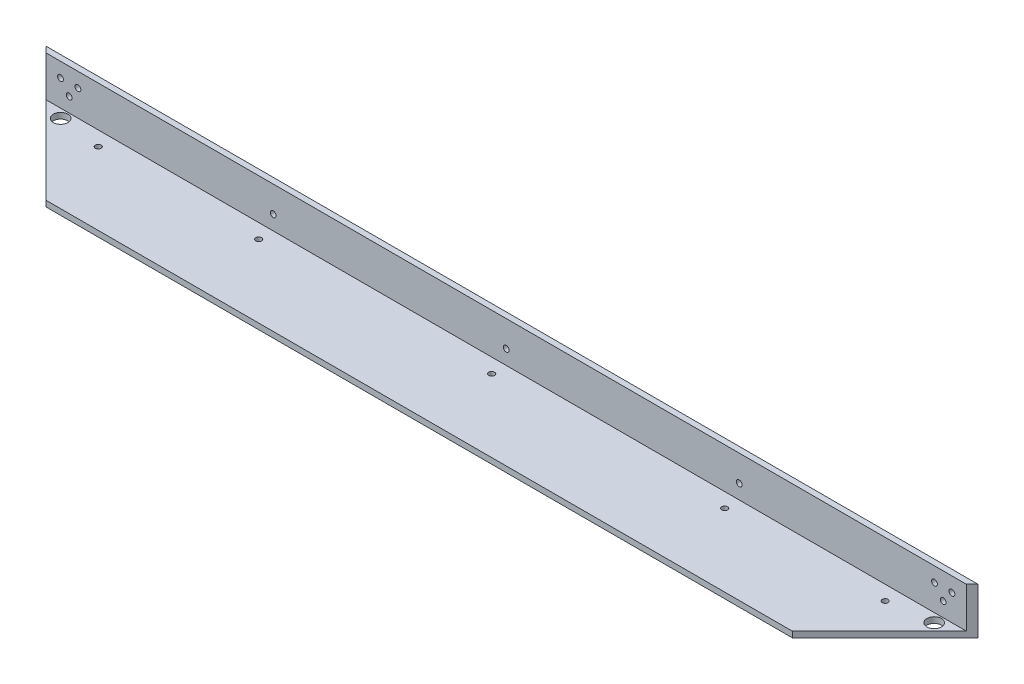
SolidWorks part; units mm, degrees
ref_plane "Front Plane" through (0, 0, 0) normal (0, 0, 1) x (1, 0, 0)
ref_plane "Top Plane" through (0, 0, 0) normal (0, 1, 0) x (1, 0, 0)
ref_plane "Right Plane" through (0, 0, 0) normal (1, 0, 0) x (0, 0, -1)
sketch "Sketch1" plane through (0, 0, 0) normal (1, 0, 0) x (0, 0, -1)
  line L0 (0, 0) -> (-50.8, 0)
  line L1 (-50.8, 0) -> (-50.8, 3.175)
  line L2 (-50.8, 3.175) -> (-3.175, 3.175)
  line L3 (-3.175, 3.175) -> (-3.175, 25.4)
  line L4 (-3.175, 25.4) -> (0, 25.4)
  line L5 (0, 25.4) -> (0, 0)
  dimension "LHeight" = 25.4
  dimension "LWidth" = 50.8
  dimension "LMaterialThickness" = 3.175
  dimension "D1" = 47.625
  dimension "D2" = 22.225
  dimension "D3" = 3.175
extrude "Boss-Extrude1" add sketch "Sketch1" along normal blind 510
chamfer "Chamfer6" distance 50.8 angle 45 1 edges at (510, 1.5875, 50.8)
chamfer "Chamfer7" distance 50.8 angle 45 1 edges at (0, 1.5875, 50.8)
sketch "BackSideHoles-Sketch2" plane through (0, 0, 0) normal (0, 0, -1) x (-1, 0, 0)
  line L0 (0, 0) -> (0, 25.4) construction
  line L1 (-510, 0) -> (0, 0) construction
  line L2 (-510, 0) -> (-510, 25.4) construction
  line L3 (-510, 25.4) -> (0, 25.4) construction
  circle A0 centre (-498.8875, 17.4625) radius 1.5875
  circle A1 centre (-489.3625, 17.4625) radius 1.5875
  circle A2 centre (-20.6375, 17.4625) radius 1.5875
  circle A4 centre (-11.1125, 17.4625) radius 1.5875
  circle A5 centre (-15.875, 11.1125) radius 1.5875
  circle A6 centre (-494.125, 11.1125) radius 1.5875
  circle A8 centre (-382.5, 11.1125) radius 1.5875
  circle A9 centre (-255, 11.1125) radius 1.5875
  circle A10 centre (-127.5, 11.1125) radius 1.5875
  dimension "D5" = 3.175
  dimension "D2" = 20.6375
  dimension "D4" = 20.6375
  dimension "D8" = 127.5
  dimension "D9" = 127.5
  dimension "D10" = 127.5
  dimension "D11" = 11.1125
  dimension "D6" = 7.9375
  dimension "D7" = 11.1125
  dimension "D3" = 11.1125
  dimension "D12" = 15.875
  dimension "D13" = 15.875
sketch "BottomHoles-Sketch3" plane through (0, 0, 0) normal (0, -1, 0) x (1, 0, 0)
  line L0 (510, 0) -> (0, 0) construction
  circle A7 centre (39.6875, 11.1125) radius 1.5875
  circle A8 centre (470.3125, 11.1125) radius 1.5875
  circle A9 centre (127.5, 11.1125) radius 1.5875
  circle A10 centre (255, 11.1125) radius 1.5875
  circle A11 centre (382.5, 11.1125) radius 1.5875
  circle A12 centre (494, 8) radius 4
  circle A13 centre (16, 8) radius 4
  point P21 (13.8721, 4.5045)
  dimension "D5" = 3.175
  dimension "D11" = 8
  dimension "D2" = 39.6875
  dimension "D3" = 39.6875
  dimension "D4" = 11.1125
  dimension "D1" = 127.5
  dimension "D6" = 127.5
  dimension "D7" = 127.5
  dimension "D8" = 16
  dimension "D9" = 8
  dimension "D10" = 16
extrude "BottomHoles-Cut-Extrude1" cut sketch "BottomHoles-Sketch3" against normal through all
extrude "BackSideHoles-Cut-Extrude2" cut sketch "BackSideHoles-Sketch2" against normal through all
equation "\"LowerRailWidth\"= 2.00in"
equation "\"LowerRailHeight\"= 1.00in"
equation "\"RailThickness\"= .125in'Spec"
equation "\"SideRailHoleX1FromSide\"= \"HoleOffsetFromSide\""
equation "\"SideRailHoleX2FromSide\"= \"VSWidth\" - \"HoleOffsetFromEdge\" - \"RailThickness\"'Equals 20.6375"
equation "\"SideRailHoleY1FromEdge\"= \"HoleOffsetFromEdge\""
equation "\"FrontBackRailLength\"= 510mm"
equation "\"VSWidth\"= 1.25in'Spec"
equation "\"HoleOffsetFromEdge\"= \"RailThickness\" * 2.5"
equation "\"HoleOffsetFromSide\"= \"RailThickness\" * 3.5"
equation "\"SideRailHoleY2FromSide\"= \"HoleOffsetFromSide\""
equation "\"FasteningHoleDiameter\"= .125in"
equation "\"D1@Boss-Extrude1\"=\"FrontBackRailLength\""
equation "\"D1@Chamfer6\"=\"LowerRailWidth\""
equation "\"D1@Chamfer7\"=\"LowerRailWidth\""
equation "\"D2@BackSideHoles-Sketch2\" = \"SideRailHoleX2FromSide\""
equation "\"D4@BackSideHoles-Sketch2\" = \"SideRailHoleX2FromSide\""
equation "\"D5@BackSideHoles-Sketch2\" = \"FasteningHoleDiameter\""
equation "\"LHeight@Sketch1\"=\"LowerRailHeight\""
equation "\"LWidth@Sketch1\"=\"LowerRailWidth\""
equation "\"LowerCornerBlockWidth\"= \"LowerRailWidth\" - \"RailThickness\" * 2'Room for left front stepper"
equation "\"D2@BottomHoles-Sketch3\"=\"CornerEnclosureOffset\""
equation "\"D3@BottomHoles-Sketch3\"=\"CornerEnclosureOffset\""
equation "\"D4@BottomHoles-Sketch3\"=\"LowerCornerBlockY1FromSide\""
equation "\"D5@BottomHoles-Sketch3\"=\"FasteningHoleDiameter\""
equation "\"CornerEnclosureOffset\"= \"LowerCornerBlockWidth\" - \"HoleOffsetFromEdge\" + \"RailThickness\""
equation "\"LowerCornerBlockY1FromSide\"= \"HoleOffsetFromSide\""
equation "\"FrontOrBackEnclosureOffsets\"= \"FrontBackRailLength\" / 4"
equation "\"D1@BottomHoles-Sketch3\"=\"FrontOrBackEnclosureOffsets\""
equation "\"D6@BottomHoles-Sketch3\"=\"FrontOrBackEnclosureOffsets\""
equation "\"D7@BottomHoles-Sketch3\"=\"FrontOrBackEnclosureOffsets\""
equation "\"D8@BackSideHoles-Sketch2\"=\"FrontOrBackEnclosureOffsets\""
equation "\"D9@BackSideHoles-Sketch2\"=\"FrontOrBackEnclosureOffsets\""
equation "\"D10@BackSideHoles-Sketch2\"=\"FrontOrBackEnclosureOffsets\""
equation "\"D11@BackSideHoles-Sketch2\"=\"SideRailHoleX1FromSide\""
equation "\"D6@BackSideHoles-Sketch2\"=\"SideRailHoleY1FromEdge\""
equation "\"D7@BackSideHoles-Sketch2\"=\"SideRailHoleY2FromSide\""
equation "\"D3@BackSideHoles-Sketch2\"=\"SideRailHoleX1FromSide\""
equation "\"VSMidSideRailHoleXFromSideToCenter\"= \"RailThickness\" * 6"
equation "\"D12@BackSideHoles-Sketch2\"=\"VSMidSideRailHoleXFromSideToCenter\" - \"RailThickness\""
equation "\"D13@BackSideHoles-Sketch2\"=\"VSMidSideRailHoleXFromSideToCenter\" - \"RailThickness\""
equation "\"LowerRailCableHoleDiameter\"= 8mm"
equation "\"LowerRailCableHoleOffsetFromSide\"= 8mm"
equation "\"LowerRailCableHoleOffsetFromEdge\"= 16mm"
equation "\"D8@BottomHoles-Sketch3\"=\"LowerRailCableHoleOffsetFromEdge\""
equation "\"D9@BottomHoles-Sketch3\"=\"LowerRailCableHoleOffsetFromSide\""
equation "\"D10@BottomHoles-Sketch3\"=\"LowerRailCableHoleOffsetFromEdge\""
equation "\"D11@BottomHoles-Sketch3\"=\"LowerRailCableHoleDiameter\""
